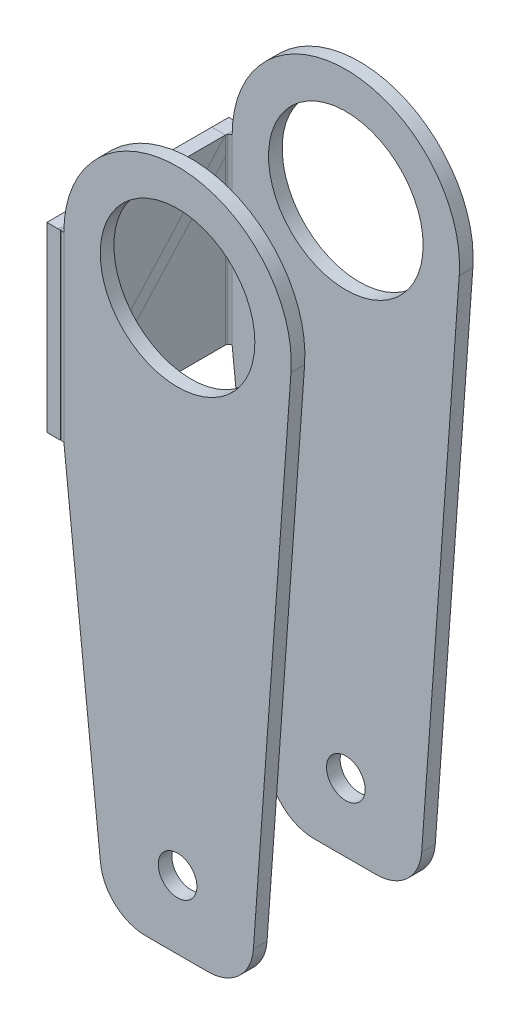
SolidWorks part; units mm, degrees
note: The reader was unsure of these and kept them because the rebuilt part matched: flange length of "Edge-Flange1".
ref_plane "Front Plane" through (0, 0, 0) normal (0, 0, 1) x (1, 0, 0)
ref_plane "Top Plane" through (0, 0, 0) normal (0, 1, 0) x (1, 0, 0)
ref_plane "Right Plane" through (0, 0, 0) normal (1, 0, 0) x (0, 0, -1)
sketch "Sketch1" plane through (0, 0, 0) normal (0, 0, 1) x (1, 0, 0)
  line L2 (0, 40) -> (0, 0)
  line L4 (0, 0) -> (9, -85)
  line L5 (9, -85) -> (41, -85)
  line L6 (41, -85) -> (49.9345, 38.1916)
  line L7 (25, 40) -> (25, -70) construction
  circle A0 centre (25, 40) radius 17
  circle A1 centre (25, -70) radius 4.25
  arc A2 (49.9345, 38.1916) -> (0, 40) centre (25, 40) ccw
  dimension "D3" = 34
  dimension "D4" = 110
  dimension "D5" = 50
  dimension "D6" = 8.5
  dimension "D8" = 16
  dimension "D1" = 125
  dimension "D2" = 40
  dimension "D7" = 32
base flange "Base-Flange1" sketch "Sketch1" thickness 3 reverse thickness direction no parameters "D1"=0.7366
edge flange "Edge-Flange1" sketch "Sketch8" flange angle 90 flange length 40 flange position bend outside bend radius 0.7366 thickness 3 relief rectangular parameters "D6"=10
sketch "Sketch8" plane through (0, 0, 0) normal (-1, 0, 0) x (0, -1, 0)
  line L0 (-40, 0) -> (0, 0) construction
  line L1 (-40, 0) -> (0, 0)
  line L2 (-40, 0) -> (-40, 37)
  line L3 (-40, 37) -> (0, 37)
  line L4 (0, 37) -> (0, 0)
bend "EdgeBend1" bend radius 0.7366 bend angle 90 parameters "D5"=1
ref_plane "Plane1" through (0, 0, 17) normal (0, 0, -1) x (-1, 0, 0)
mirror "Mirror1" about plane through (0, 0, 17) normal (0, 0, -1) of bodies 102
bend "DerivedBend1" bend radius 0.7366 bend angle 90 parameters "D5"=1
fillet "Fillet1" radius 10 2 edges at (9, -85, 35.5) (41, -85, 35.5)
fillet "Fillet2" radius 10 2 edges at (41, -85, -1.5) (9, -85, -1.5)
sketch "Bend-Lines1" [suppressed] plane through (0, 0, 0) normal (0, 1, 0) x (1, 0, 0)
sketch "Bounding-Box1" [suppressed] plane through (0, 0, 0) normal (0, 1, 0) x (1, 0, 0)
sheet metal parameters "Sheet-Metal1" thickness 3 parameters "D1"=0.7366
flat pattern "Flat-Pattern1" [suppressed]
sketch "Bend-Lines2" plane through (0, 0, 0) normal (0, 1, 0) x (1, 0, 0)
sketch3d "Bounding-Box2" [suppressed]
  line L0 (-25, 25, 0) -> (-25, -120, 0) construction
  line L1 (25, 25, 0) -> (25, -120, 0) construction
  line L2 (-25, 25, 0) -> (25, 25, 0) construction
  line L3 (-25, -120, 0) -> (25, -120, 0) construction
sheet metal parameters "Sheet-Metal2" thickness 3 parameters "D1"=0.7366
flat pattern "Flat-Pattern1"
sketch "Bend-Lines2" plane through (0, 0, 0) normal (0, 0, 1) x (1, 0, 0)
  line L0 (-1.7566, 40) -> (-1.7566, 0) construction
  line L1 (-1.7566, 40) -> (-1.7566, 0) construction
sketch3d "Bounding-Box2" [suppressed]
  line L0 (15.8777, -126.6857, 0) -> (26.7429, 23.1261, 0) construction
  line L1 (-73.4945, -120.2039, 0) -> (-62.6293, 29.6079, 0) construction
  line L2 (15.8777, -126.6857, 0) -> (-73.4945, -120.2039, 0) construction
  line L3 (26.7429, 23.1261, 0) -> (-62.6293, 29.6079, 0) construction
bend of the flat pattern "Flatten-<EdgeBend1>1"
sheet metal parameters "Sheet-Metal3" thickness 3 parameters "D1"=0.7366
flat pattern "Flat-Pattern3"
sketch "Bend-Lines3" plane through (0, 0, 37) normal (0, 0, 1) x (1, 0, 0)
  line L0 (-1.7566, 0) -> (-1.7566, 40) construction
  line L1 (-1.7566, 0) -> (-1.7566, 40) construction
sketch3d "Bounding-Box3" [suppressed]
  line L0 (-62.6293, 29.6079, 0) -> (-73.4945, -120.2039, 0) construction
  line L1 (26.7429, 23.1261, 0) -> (15.8777, -126.6857, 0) construction
  line L2 (-62.6293, 29.6079, 0) -> (26.7429, 23.1261, 0) construction
  line L3 (-73.4945, -120.2039, 0) -> (15.8777, -126.6857, 0) construction
bend of the flat pattern "Flatten-<DerivedBend1>1"
